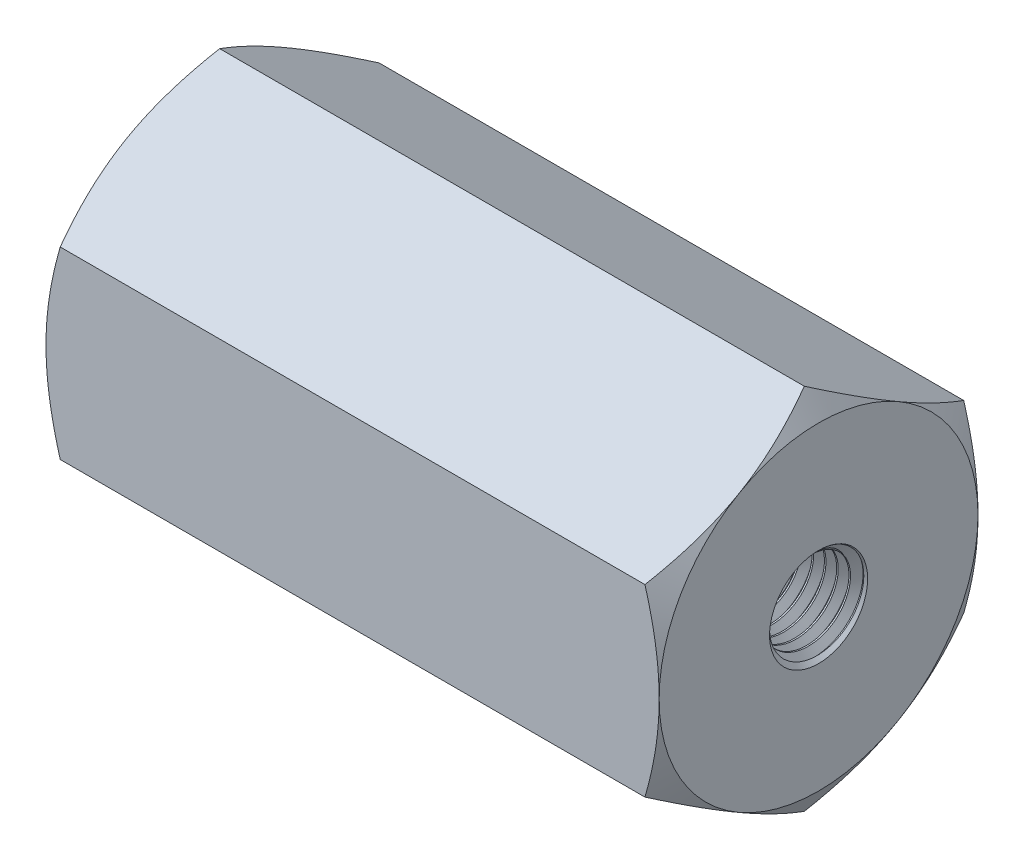
SolidWorks part; units mm, degrees
ref_plane "Front" through (0, 0, 0) normal (0, 0, 1) x (1, 0, 0)
ref_plane "Top" through (0, 0, 0) normal (0, 1, 0) x (1, 0, 0)
ref_plane "Right" through (0, 0, 0) normal (1, 0, 0) x (0, 0, -1)
sketch "Sketch1" plane through (0, 0, 0) normal (1, 0, 0) x (0, 0, -1)
  line L1 (-6.5, 3.7528) -> (-6.5, -3.7528)
  line L2 (-6.5, -3.7528) -> (0, -7.5056)
  line L3 (0, -7.5056) -> (6.5, -3.7528)
  line L4 (6.5, -3.7528) -> (6.5, 3.7528)
  line L5 (6.5, 3.7528) -> (0, 7.5056)
  line L6 (0, 7.5056) -> (-6.5, 3.7528)
  circle A0 centre (0, 0) radius 6.5 construction
  dimension "HexSize" = 13
extrude "Boss-Extrude1" add sketch "Sketch1" along normal mid plane 25
sketch "Sketch2" plane through (12.5, 0, 0) normal (1, 0, 0) x (0, 0, -1)
  circle A0 centre (0, 0) radius 6.5 construction
  circle A1 centre (0, 0) radius 6.5
extrude "Cut-Extrude1" cut sketch "Sketch2" against normal through all draft 60 flip side to cut
mirror "Mirror1" about plane through (0, 0, 0) normal (1, 0, 0) of "Cut-Extrude1"
sketch "Sketch3" plane through (12.5, 0, 0) normal (1, 0, 0) x (0, 0, -1)
  circle A0 centre (0, 0) radius 2
  dimension "ThrdSizeA" = 4
extrude "Cut-Extrude2" cut sketch "Sketch3" against normal blind 4
sketch "Sketch4" plane through (-12.5, 0, 0) normal (-1, 0, 0) x (0, 0, 1)
  circle A0 centre (0, 0) radius 2.5
  dimension "ThrdSizeB" = 5
extrude "Cut-Extrude3" cut sketch "Sketch4" against normal blind 4
sketch "Sketch7" plane through (0, 0, 0) normal (0, 0, 1) x (1, 0, 0)
  line L0 (8.5, 2) -> (12.5, 2) construction
  line L1 (8.5, 2) -> (8.5, -2) construction
  line L2 (8.5, -2) -> (12.5, -2) construction
  line L3 (-8.5, 2.5) -> (-12.5, 2.5) construction
  line L4 (-8.5, 2.5) -> (-8.5, -2.5) construction
  line L5 (-8.5, 2.5) -> (-8.5, -2.5) construction
  line L6 (-8.5, -2.5) -> (-12.5, -2.5) construction
sketch "Sketch5" plane through (-12.5, 0, 0) normal (-1, 0, 0) x (0, 0, 1)
  circle A0 centre (0, 0) radius 2.5 construction
  circle A1 centre (0, 0) radius 2.5
extrude "Boss-Extrude2" add sketch "Sketch5" against normal up to surface (4 mm away) separate body up to face at (-8.5, 0, 2.5)
sketch "Sketch6" plane through (12.5, 0, 0) normal (1, 0, 0) x (0, 0, -1)
  circle A0 centre (0, 0) radius 2 construction
  circle A1 centre (0, 0) radius 2
extrude "Boss-Extrude3" add sketch "Sketch6" against normal up to surface (4 mm away) separate body up to face at (8.5, 0, -2)
sketch "Sketch8" plane through (12.5, 0, 0) normal (1, 0, 0) x (0, 0, -1)
  circle A0 centre (0, 0) radius 2 construction
  circle A1 centre (0, 0) radius 2
curve "Helix/Spiral1" pitch 0.5 height 4.5 radius 2 centre (12.5, 0, 0) axis (-1, 0, 0) start towards (0, 1, 0) parameters "PitchA"=0.5
sketch "Sketch9" plane through (0, 0, 0) normal (0, 0, 1) x (1, 0, 0)
  line L0 (12.5, 2) -> (12.9375, 2)
  line L1 (12.9375, 2) -> (12.75, 1.6752)
  line L2 (12.75, 1.6752) -> (12.6875, 1.6752)
  line L3 (12.6875, 1.6752) -> (12.5, 2)
  line L4 (12.7187, 2) -> (12.7187, 1.6752) construction
  line L5 (12.5937, 1.8376) -> (12.8437, 1.8376) construction
  dimension "D1" = 0.0625
  dimension "D2" = 0.25
  dimension "D3" = 60
sweep "Cut-Sweep1" cut profiles "Sketch9" path "Helix/Spiral1" align with end faces yes
sketch "Sketch10" plane through (12.5, 0, 0) normal (1, 0, 0) x (0, 0, -1)
  circle A0 centre (0, 0) radius 2 construction
  circle A1 centre (0, 0) radius 2
extrude "Boss-Extrude4" add sketch "Sketch10" against normal through all draft 45
sketch "Sketch11" plane through (-12.5, 0, 0) normal (-1, 0, 0) x (0, 0, 1)
  circle A1 centre (0, 0) radius 2.5
  circle A2 centre (0, 0) radius 2.5
  dimension "D1" = 0
curve "Helix/Spiral2" pitch 0.5 height 4.5 turns 9 parameters "PitchB"=0.5
sketch "Sketch12" plane through (0, 0, 0) normal (0, 0, 1) x (1, 0, 0)
  line L0 (-12.5, 2.5) -> (-12.9375, 2.5)
  line L1 (-12.9375, 2.5) -> (-12.75, 2.1752)
  line L2 (-12.75, 2.1752) -> (-12.6875, 2.1752)
  line L3 (-12.6875, 2.1752) -> (-12.5, 2.5)
  line L4 (-12.7188, 2.5) -> (-12.7188, 2.1752) construction
  line L5 (-12.8437, 2.3376) -> (-12.5937, 2.3376) construction
  dimension "D1" = 60
  dimension "D2" = 0.0625
  dimension "D3" = 0.25
sweep "Cut-Sweep2" cut profiles "Sketch12" path "Helix/Spiral2" align with end faces yes
sketch "Sketch13" plane through (-12.5, 0, 0) normal (-1, 0, 0) x (0, 0, 1)
  circle A0 centre (0, 0) radius 2.5 construction
  circle A1 centre (0, 0) radius 2.5
extrude "Boss-Extrude5" add sketch "Sketch13" against normal through all draft 45
sketch "Sketch14" plane through (-12.5, 0, 0) normal (-1, 0, 0) x (0, 0, 1)
  arc A13 (-3.2, 5.5426) -> (-6.4, 0) centre (0, 0) ccw
  arc A14 (-6.4, 0) -> (-3.2, -5.5426) centre (0, 0) ccw
  arc A15 (-3.2, -5.5426) -> (3.2, -5.5426) centre (0, 0) ccw
  arc A16 (3.2, -5.5426) -> (6.4, 0) centre (0, 0) ccw
  arc A17 (6.4, 0) -> (3.2, 5.5426) centre (0, 0) ccw
  arc A18 (3.2, 5.5426) -> (-3.2, 5.5426) centre (0, 0) ccw
  arc A19 (-3.2, 5.5426) -> (-6.4, 0) centre (0, 0) ccw
  arc A20 (-6.4, 0) -> (-3.2, -5.5426) centre (0, 0) ccw
  arc A21 (-3.2, -5.5426) -> (3.2, -5.5426) centre (0, 0) ccw
  arc A22 (3.2, -5.5426) -> (6.4, 0) centre (0, 0) ccw
  arc A23 (6.4, 0) -> (3.2, 5.5426) centre (0, 0) ccw
  arc A24 (3.2, 5.5426) -> (-3.2, 5.5426) centre (0, 0) ccw
  dimension "D1" = 0.1
extrude "Boss-Extrude6" add sketch "Sketch14" against normal up to surface (25 mm away) up to face at (12.5, 0, -2)
combine bodies "Combine1" operation type subtract main body 120 bodies to subtract 116 118
equation "\"D3@Helix/Spiral1\"=\"ThrdDepthA@Cut-Extrude2\"+\"PitchA@Helix/Spiral1\""
equation "\"D1@Sketch9\"=\"PitchA@Helix/Spiral1\"*.125"
equation "\"D2@Sketch9\"=\"PitchA@Helix/Spiral1\"*.50"
equation "\"D3@Helix/Spiral2\"=\"ThrdDpB@Cut-Extrude3\"+\"PitchB@Helix/Spiral2\""
equation "\"D2@Sketch12\"=\"PitchB@Helix/Spiral2\"*.125"
equation "\"D3@Sketch12\"=\"PitchB@Helix/Spiral2\"*.50"
